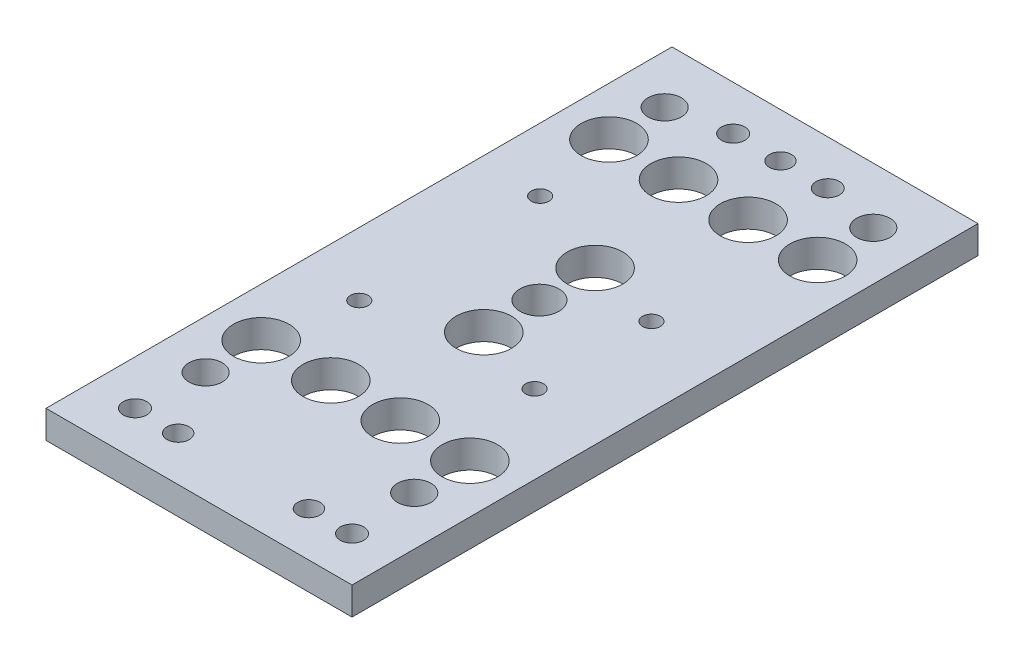
SolidWorks part; units mm, degrees
material "K110"
ref_plane "Front Plane" through (0, 0, 0) normal (0, 0, 1) x (1, 0, 0)
ref_plane "Top Plane" through (0, 0, 0) normal (0, 1, 0) x (1, 0, 0)
ref_plane "Right Plane" through (0, 0, 0) normal (1, 0, 0) x (0, 0, -1)
sketch "Sketch1" plane through (0, 0, 0) normal (0, 1, 0) x (1, 0, 0)
  line L1 (-55, -112.5) -> (55, -112.5)
  line L2 (-55, -112.5) -> (-55, 112.5)
  line L3 (-55, 112.5) -> (55, 112.5)
  line L4 (55, -112.5) -> (55, 112.5)
  line L5 (-55, -112.5) -> (55, 112.5) construction
  line L6 (-55, 112.5) -> (55, -112.5) construction
  point P0 (0, 0)
  dimension "D1" = 225
  dimension "D2" = 110
extrude "Boss-Extrude1" add sketch "Sketch1" against normal blind 10
hole_wizard "M8 Clearance Hole1" positions "Sketch4" profile "Sketch3" hole size "M8" standard "ISO" end condition through all
sketch "Sketch4" plane through (0, 0, 0) normal (0, 1, 0) x (1, 0, 0)
  point P0 (-17, 96.5)
  point P3 (17, 96.5)
  point P6 (-39, -96.5)
  point P9 (39, -96.5)
sketch "Sketch3" plane through (-17, 0, -96.5) normal (1, 0, 0) x (0, 0, 1)
  line L0 (0, 0) -> (0, 10)
  line L1 (0, 10) -> (4.2, 10)
  line L2 (4.2, 10) -> (4.2, 0)
  line L5 (4.2, 0) -> (0, 0)
  line L11 (0, -6.35) -> (0, 107.95) construction
  dimension "Thru Hole Dia." = 8.4
  dimension "Thru Hole Depth" = 10
hole_wizard "Ø8.0mm Dowel Hole1" positions "Sketch7" profile "Sketch6" hole size "Ø8.0" standard "ISO" end condition through all
sketch "Sketch7" plane through (0, 0, 0) normal (0, 1, 0) x (1, 0, 0)
  point P0 (0, 96.5)
  point P3 (-23.5, -96.5)
  point P6 (23.5, -96.5)
sketch "Sketch6" plane through (0, 0, -96.5) normal (1, 0, 0) x (0, 0, 1)
  line L0 (0, 0) -> (0, 10)
  line L1 (0, 10) -> (4, 10)
  line L2 (4, 10) -> (4, 0)
  line L5 (4, 0) -> (0, 0)
  line L11 (0, -6.35) -> (0, 107.95) construction
  dimension "Thru Hole Dia." = 8
  dimension "Thru Hole Depth" = 10
sketch "Sketch8" plane through (0, 0, 0) normal (0, 1, 0) x (1, 0, 0)
  circle A0 centre (0, 9.86) radius 7
  dimension "D1" = 14
extrude "Cut-Extrude1" cut sketch "Sketch8" against normal up to next
hole_wizard "M6 Clearance Hole1" positions "Sketch12" profile "Sketch10" hole size "M6" standard "ISO" end condition through all
sketch "Sketch12" plane through (0, 0, 0) normal (0, 1, 0) x (1, 0, 0)
  point P6 (26.75, 23.36)
  point P9 (26.75, -18.64)
  point P16 (-32.25, 42.36)
  point P19 (-32.25, -22.64)
sketch "Sketch10" plane through (26.75, 0, -23.36) normal (1, 0, 0) x (0, 0, 1)
  line L0 (0, 0) -> (0, 10)
  line L1 (0, 10) -> (3.2, 10)
  line L2 (3.2, 10) -> (3.2, 0)
  line L5 (3.2, 0) -> (0, 0)
  line L11 (0, -6.35) -> (0, 107.95) construction
  dimension "Thru Hole Dia." = 6.4
  dimension "Thru Hole Depth" = 10
sketch "Sketch14" plane through (0, 0, 0) normal (0, 1, 0) x (1, 0, 0)
  circle A0 centre (37.5, 72.36) radius 10
  circle A1 centre (12.5, 72.36) radius 10
  circle A2 centre (-12.5, 72.36) radius 10
  circle A3 centre (-37.5, 72.36) radius 10
  circle A4 centre (0, 29.86) radius 10
  circle A5 centre (0, -10.14) radius 10
  circle A6 centre (37.5, -52.64) radius 10
  circle A7 centre (12.5, -52.64) radius 10
  circle A8 centre (-12.5, -52.64) radius 10
  circle A9 centre (-37.5, -52.64) radius 10
  dimension "D1" = 20
extrude "Cut-Extrude2" cut sketch "Sketch14" against normal through all
sketch "Sketch15" plane through (0, 0, 0) normal (0, 1, 0) x (1, 0, 0)
  circle A0 centre (37.5, -72.64) radius 6 construction
  circle A1 centre (-37.5, -72.64) radius 6 construction
  circle A2 centre (-37.5, 92.36) radius 6 construction
  circle A3 centre (37.5, 92.36) radius 6 construction
  circle A4 centre (37.5, -72.64) radius 6
  circle A5 centre (-37.5, -72.64) radius 6
  circle A6 centre (-37.5, 92.36) radius 6
  circle A7 centre (37.5, 92.36) radius 6
extrude "Cut-Extrude3" cut sketch "Sketch15" against normal through all
